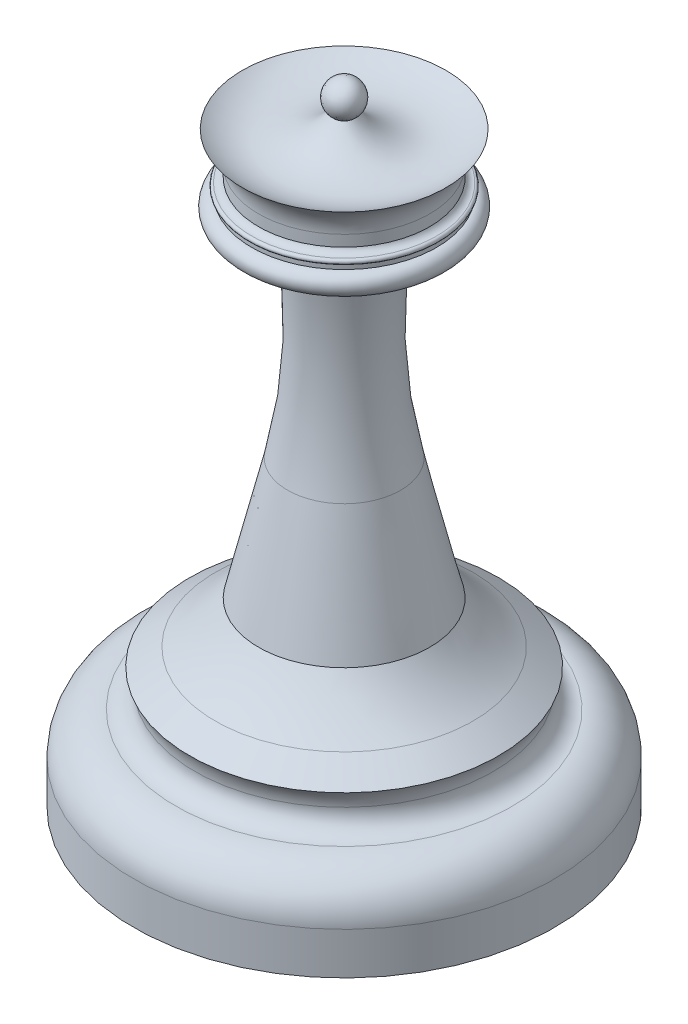
SolidWorks part; units mm, degrees
material "PVC Rigid"
ref_plane "Front Plane" through (0, 0, 0) normal (0, 0, 1) x (1, 0, 0)
ref_plane "Top Plane" through (0, 0, 0) normal (0, 1, 0) x (1, 0, 0)
ref_plane "Right Plane" through (0, 0, 0) normal (1, 0, 0) x (0, 0, -1)
sketch "Sketch1" plane through (0, 0, 0) normal (0, 0, 1) x (1, 0, 0)
  line L0 (0, 0) -> (-10, 0)
  line L3 (-9.9997, 2) -> (-10, 0)
  line L11 (0, 0) -> (0, 36.8797) construction
  line L18 (-7.3467, 5.7487) -> (-6.1296, 6.5718)
  line L19 (-4.0678, 8.5804) -> (-2.69, 14.3603)
  line L20 (-2.4418, 24.2158) -> (-4.3963, 24.2158)
  line L21 (-4.3963, 25.21) -> (-4.3963, 25.4429)
  line L22 (-4.0678, 25.8995) -> (-4.0678, 26.4287)
  line L23 (0, 30) -> (0, 0)
  arc A0 (-8.0003, 3.9997) -> (-9.9997, 2) centre (-7.9997, 1.9997) ccw
  arc A11 (-8.0003, 3.9997) -> (-7.084, 4.9669) centre (-8.0006, 4.9176) ccw
  arc A12 (-7.084, 4.9669) -> (-7.3467, 5.7487) centre (-8.6254, 4.884) ccw
  arc A13 (-6.1296, 6.5718) -> (-4.0678, 8.5804) centre (-10.6895, 13.3149) ccw
  arc A14 (-2.69, 14.3603) -> (-2.4418, 24.2158) centre (-25.8184, 19.8738) ccw
  arc A15 (-4.3963, 24.2158) -> (-4.3963, 25.21) centre (-4.3963, 24.7129) cw
  arc A16 (-4.3963, 25.4429) -> (-4.3963, 25.6804) centre (-4.3963, 25.5616) cw
  arc A17 (-4.3963, 25.6804) -> (-4.0678, 25.8995) centre (-4.3963, 26.036) ccw
  arc A18 (-4.0678, 26.4287) -> (-4.0678, 26.7561) centre (-4.0678, 26.5924) cw
  arc A19 (-4.0678, 26.4287) -> (-4.8406, 27.8912) centre (-5.8382, 26.4287) ccw
  arc A20 (-4.8406, 27.8912) -> (-0.4915, 28.5685) centre (-3.0273, 30.5495) ccw
  circle A21 centre (0, 29.1999) radius 0.8001 construction
  arc A22 (-0.4915, 28.5685) -> (0, 30) centre (0.0013, 29.1994) cw
  point P32 (-4.0678, 8.5804)
  point P34 (-2.4418, 16.5143)
  point P37 (0, 0)
  point P38 (0, 0)
  dimension "D2" = 3.2179
  dimension "D6" = 0.1637
  dimension "D4" = 1.7703
  dimension "D3" = 0.8006
  dimension "D8" = 0.3557
  dimension "D9" = 0.1187
  dimension "D11" = 0.4971
  dimension "D13" = 8.1402
  dimension "D15" = 1.5436
  dimension "D16" = 0.918
  dimension "D17" = 2
  dimension "D1" = 2
  dimension "D5" = 10
  dimension "D7" = 0.5292
  dimension "D10" = 0.233
  dimension "D12" = 1.9545
  dimension "D14" = 1.4693
  dimension "D18" = 30
revolve "Revolve6" add sketch "Sketch1" angle 360 about L11 region at (-2.9713, 10.5116, 0)
